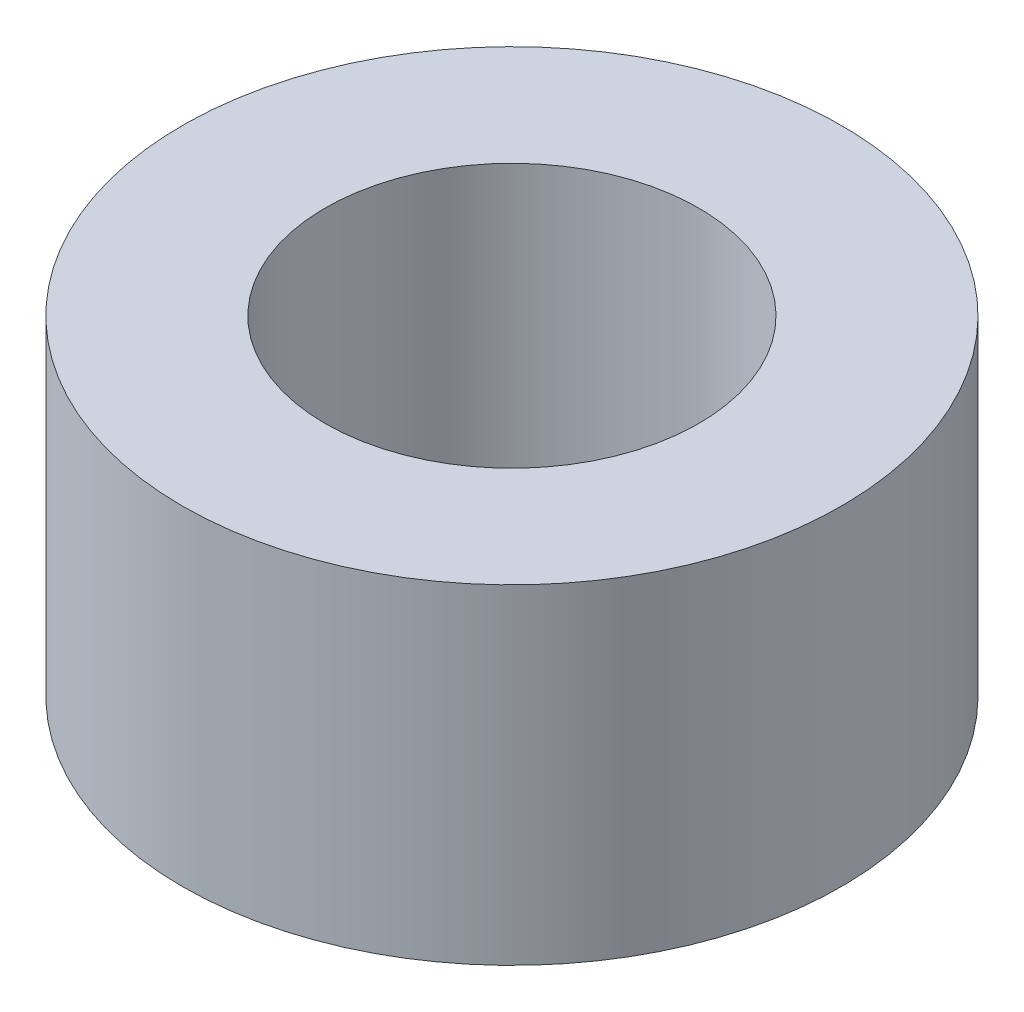
SolidWorks part; units mm, degrees
ref_plane "Front Plane" through (0, 0, 0) normal (0, 0, 1) x (1, 0, 0)
ref_plane "Top Plane" through (0, 0, 0) normal (0, 1, 0) x (1, 0, 0)
ref_plane "Right Plane" through (0, 0, 0) normal (1, 0, 0) x (0, 0, -1)
sketch "Sketch1" plane through (0, 0, 0) normal (0, 1, 0) x (1, 0, 0)
  circle A1 centre (0, 0) radius 1.7
  circle A3 centre (0, 0) radius 3
  dimension "D2" = 3.4
  dimension "D4" = 6
extrude "Boss-Extrude1" add sketch "Sketch1" along normal blind 3 contours A1 | A3 region at (0, 0, 0)
